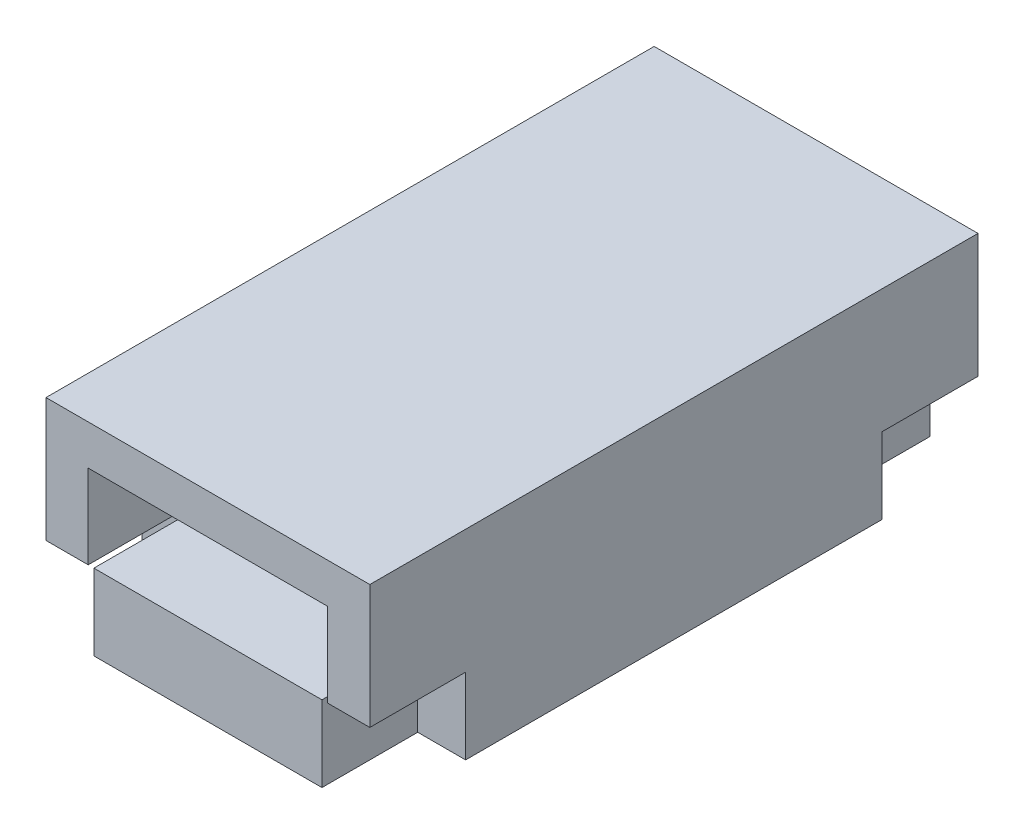
SolidWorks part; units mm, degrees
ref_plane "Front Plane" through (0, 0, 0) normal (0, 0, 1) x (1, 0, 0)
ref_plane "Top Plane" through (0, 0, 0) normal (0, 1, 0) x (1, 0, 0)
ref_plane "Right Plane" through (0, 0, 0) normal (1, 0, 0) x (0, 0, -1)
other "Center of Mass"
sketch "Sketch1" plane through (0, 0, 0) normal (0, 0, 1) x (1, 0, 0)
  line L0 (0, 1.75) -> (0, 2.4812) construction
  line L1 (5, 1.75) -> (-5, 1.75)
  line L2 (5, 1.75) -> (5, -1.75)
  line L3 (5, -1.75) -> (-5, -1.75)
  line L4 (-5, 1.75) -> (-5, -1.75)
  line L5 (5, 1.75) -> (-5, -1.75) construction
  line L6 (5, -1.75) -> (-5, 1.75) construction
  line L7 (-6.7625, 2.4812) -> (6.7625, 2.4812)
  line L8 (-6.7625, 2.4812) -> (-6.7625, -4.925)
  line L9 (-6.7625, -4.925) -> (6.7625, -4.925)
  line L10 (6.7625, 2.4812) -> (6.7625, -4.925)
  point P0 (0, 0)
  dimension "D1" = 10
  dimension "D2" = 3.5
  dimension "D3" = 13.525
  dimension "D4" = 7.4062
  dimension "D5" = 3.175
extrude "Boss-Extrude1" add sketch "Sketch1" along normal mid plane 25.4
sketch "Sketch2" plane through (0, 0, 12.7) normal (0, 0, 1) x (1, 0, 0)
  line L1 (-6.7625, -4.925) -> (-4.7625, -4.925)
  line L2 (-6.7625, -4.925) -> (-6.7625, -1.75)
  line L3 (-6.7625, -1.75) -> (-4.7625, -1.75)
  line L4 (-4.7625, -4.925) -> (-4.7625, -1.75)
  line L5 (6.7625, -4.925) -> (4.7625, -4.925)
  line L6 (6.7625, -4.925) -> (6.7625, -1.75)
  line L7 (6.7625, -1.75) -> (4.7625, -1.75)
  line L8 (4.7625, -4.925) -> (4.7625, -1.75)
  line L9 (-6.7625, 2.4812) -> (6.7625, 2.4812)
  line L10 (-6.7625, 2.4812) -> (-6.7625, 3.4202)
  line L11 (-6.7625, 3.4202) -> (6.7625, 3.4202)
  line L12 (6.7625, 2.4812) -> (6.7625, 3.4202)
  line L15 (-5, -1.75) -> (5, -1.75) construction
  line M9 (-6.7625, 2.4812) -> (-6.7625, -4.925)
  line M10 (-6.7625, -4.925) -> (6.7625, -4.925)
  line M11 (6.7625, -4.925) -> (6.7625, 2.4812)
  line M12 (6.7625, 2.4812) -> (-6.7625, 2.4812)
  line M14 (-5, -1.75) -> (-5, 1.75)
  line M16 (5, 1.75) -> (5, -1.75)
  dimension "D1" = 0.939
  dimension "D2" = 9.525
extrude "Cut-Extrude2" cut sketch "Sketch2" against normal blind 4 contours L4 L3 M10 M14 M9 | L8 L7 M10 M11 M16 region at (-5.7625, -3.3375, 12.7) region at (5.7625, -3.3375, 12.7)
extrude "Boss-Extrude2" add sketch "Sketch2<4>" against normal blind 12.7 contours L12 L11 L10 M12 region at (0, 2.9507, 12.7)
sketch "Sketch2<4>" plane through (0, 0, 12.7) normal (0, 0, 1) x (1, 0, 0) same geometry as "Sketch2"
mirror "Mirror1" about plane through (0, 0, 0) normal (0, 0, 1) of "Boss-Extrude2", "Cut-Extrude2"
